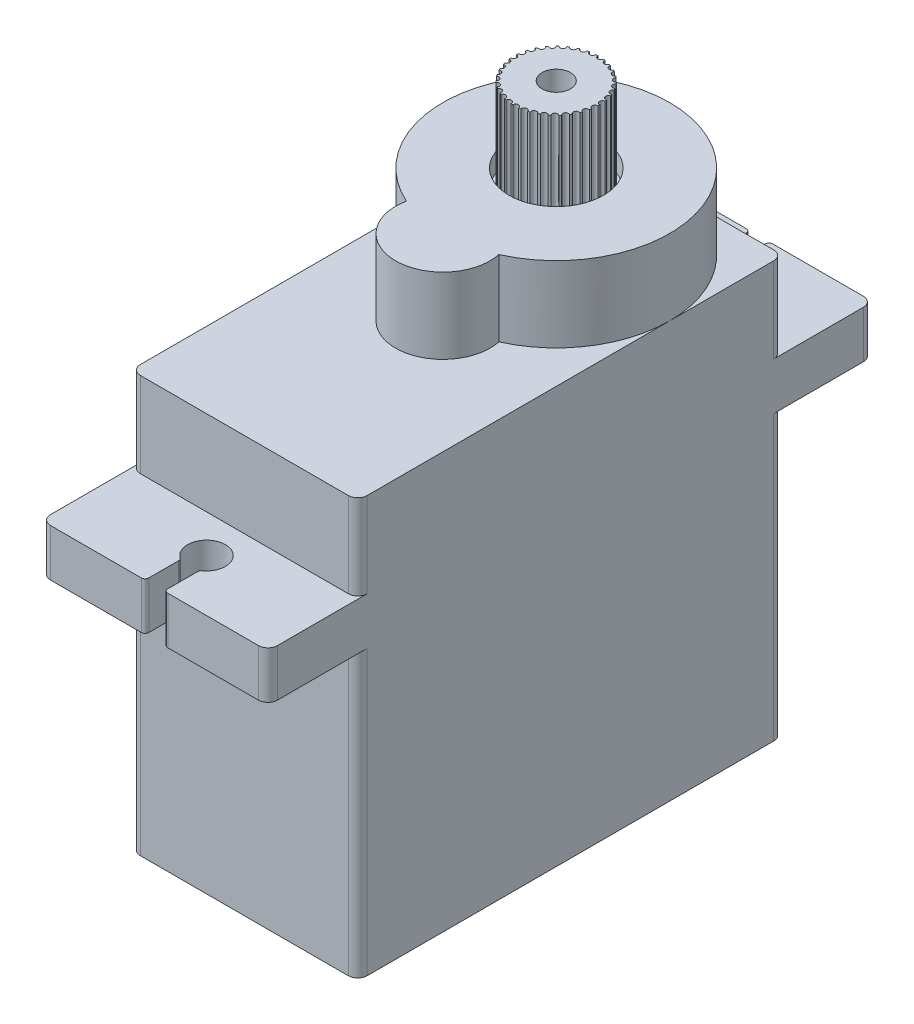
SolidWorks part; units mm, degrees
ref_plane "Ön Düzlem" through (0, 0, 0) normal (0, 0, 1) x (1, 0, 0)
ref_plane "Üst Düzlem" through (0, 0, 0) normal (0, 1, 0) x (1, 0, 0)
ref_plane "Sağ Düzlem" through (0, 0, 0) normal (1, 0, 0) x (0, 0, -1)
sketch "Çizim1" plane through (0, 0, 0) normal (0, 1, 0) x (1, 0, 0)
  line L1 (-5.5, 11.25) -> (5.5, 11.25)
  line L2 (-6, 10.75) -> (-6, -10.75)
  line L3 (-5.5, -11.25) -> (5.5, -11.25)
  line L4 (6, 10.75) -> (6, -10.75)
  line L5 (-6, 11.25) -> (6, -11.25) construction
  line L6 (-6, -11.25) -> (6, 11.25) construction
  arc A0 (5.5, -11.25) -> (6, -10.75) centre (5.5, -10.75) ccw
  arc A1 (-6, -10.75) -> (-5.5, -11.25) centre (-5.5, -10.75) ccw
  arc A2 (5.5, 11.25) -> (6, 10.75) centre (5.5, 10.75) cw
  arc A3 (-5.5, 11.25) -> (-6, 10.75) centre (-5.5, 10.75) ccw
  point P0 (0, 0)
  dimension "D3" = 0.5
  dimension "D1" = 12
  dimension "D2" = 22.5
extrude "Yükseklik-Ekstrüzyon1" add sketch "Çizim1" along normal blind 1
sketch "Çizim2" plane through (0, 1, 0) normal (0, 1, 0) x (1, 0, 0)
  line L0 (-5, 9.25) -> (-5, -9.25)
  line L1 (-5.5, 11.25) -> (5.5, 11.25)
  line L2 (-6, 10.75) -> (-6, -10.75)
  line L3 (-5.5, -11.25) -> (5.5, -11.25)
  line L4 (6, 10.75) -> (6, -10.75)
  line L5 (-6, 11.25) -> (-5.8961, 11.0552) construction
  line L6 (-6, -11.25) -> (-5.8961, -11.0552) construction
  line L7 (-4, -10.25) -> (4, -10.25)
  line L8 (5, 9.25) -> (5, -9.25)
  line L9 (-4, 10.25) -> (4, 10.25)
  line L10 (-6, -11.25) -> (6, -11.25) construction
  line L11 (6, 11.25) -> (6, -11.25) construction
  line L12 (-6, 11.25) -> (-6, -11.25) construction
  line L13 (-6, 11.25) -> (6, 11.25) construction
  line L14 (-5, 10.25) -> (5, 10.25) construction
  line L15 (-5, 10.25) -> (-5, -10.25) construction
  line L16 (-4.9345, 9.2521) -> (4.9345, -9.2521) construction
  line L17 (5, 10.25) -> (5, -10.25) construction
  line L18 (5.8961, 11.0552) -> (6, 11.25) construction
  line L19 (-5, -10.25) -> (5, -10.25) construction
  line L20 (5.8961, -11.0552) -> (6, -11.25) construction
  line L21 (-4.9345, -9.2521) -> (4.9345, 9.2521) construction
  arc A0 (5.5, -11.25) -> (6, -10.75) centre (5.5, -10.75) ccw
  arc A1 (-6, -10.75) -> (-5.5, -11.25) centre (-5.5, -10.75) ccw
  arc A2 (5.5, 11.25) -> (6, 10.75) centre (5.5, 10.75) cw
  arc A3 (-5.5, 11.25) -> (-6, 10.75) centre (-5.5, 10.75) ccw
  arc A5 (4, 10.25) -> (5, 9.25) centre (5, 10.25) ccw
  arc A7 (-4, -10.25) -> (-5, -9.25) centre (-5, -10.25) ccw
  arc A8 (-5, 9.25) -> (-4, 10.25) centre (-5, 10.25) ccw
  arc A9 (5, -9.25) -> (4, -10.25) centre (5, -10.25) ccw
  point P0 (0, 0)
  dimension "D2" = 0.5
  dimension "D1" = 1
extrude "Yükseklik-Ekstrüzyon2" add sketch "Çizim2" along normal blind 5
sketch "Çizim3" plane through (0, 6, 0) normal (0, 1, 0) x (1, 0, 0)
  line L0 (0, -10.25) -> (0, -11.25) construction
  line L1 (-4, -10.25) -> (4, -10.25) construction
  line L2 (-5.5, -11.25) -> (5.5, -11.25) construction
  line L3 (0, -11.25) -> (0, -10.75) construction
  line L4 (0, -10.75) -> (2.4368, -10.75) construction
  line L6 (-2, -10.25) -> (2, -10.25)
  line L7 (-2, -10.25) -> (-2, -11.25)
  line L8 (-2, -11.25) -> (2, -11.25)
  line L9 (2, -10.25) -> (2, -11.25)
  line L10 (-2, -10.25) -> (2, -11.25) construction
  line L11 (-2, -11.25) -> (2, -10.25) construction
  dimension "D1" = 4
extrude "Kes-Ekstrüzyon1" cut sketch "Çizim3" against normal blind 1
fillet "Radyus1" radius 0.1 2 edges at (2, 5, 10.75) (-2, 5, 10.75)
sketch "Çizim4" plane through (0, 6, 0) normal (0, 1, 0) x (1, 0, 0)
  line L0 (-4, 10.25) -> (4, 10.25)
  line L1 (-5.5, 11.25) -> (5.5, 11.25)
  line L2 (-6, 10.75) -> (-6, -10.75)
  line L3 (-5.5, -11.25) -> (5.5, -11.25)
  line L4 (6, 10.75) -> (6, -10.75)
  line L5 (-6, 11.25) -> (-5.8961, 11.0552) construction
  line L6 (-6, -11.25) -> (-5.8961, -11.0552) construction
  line L7 (-4, 10.25) -> (4, 10.25)
  line L8 (5, 9.25) -> (5, -9.25)
  line L9 (5, -9.25) -> (5, 9.25)
  line L10 (-4, 10.25) -> (4, 10.25)
  line L11 (5, 9.25) -> (5, -9.25)
  line L12 (-4, -10.25) -> (4, -10.25)
  line L13 (-5, 9.25) -> (-5, -9.25)
  line L14 (-4.9345, 9.2521) -> (4.9345, -9.2521) construction
  line L15 (-5, 10.25) -> (-5, -10.25) construction
  line L16 (-5, 10.25) -> (5, 10.25) construction
  line L17 (5, 10.25) -> (5, -10.25) construction
  line L18 (5.8961, 11.0552) -> (6, 11.25) construction
  line L19 (5.8961, -11.0552) -> (6, -11.25) construction
  line L20 (-5, -10.25) -> (5, -10.25) construction
  line L21 (-4.9345, -9.2521) -> (4.9345, 9.2521) construction
  arc A0 (5.5, -11.25) -> (6, -10.75) centre (5.5, -10.75) ccw
  arc A1 (-6, -10.75) -> (-5.5, -11.25) centre (-5.5, -10.75) ccw
  arc A2 (5.5, 11.25) -> (6, 10.75) centre (5.5, 10.75) cw
  arc A3 (-5.5, 11.25) -> (-6, 10.75) centre (-5.5, 10.75) ccw
  arc A4 (-5, 9.25) -> (-4, 10.25) centre (-5, 10.25) ccw
  arc A5 (4, 10.25) -> (5, 9.25) centre (5, 10.25) ccw
  arc A6 (-4, -10.25) -> (-5, -9.25) centre (-5, -10.25) ccw
  arc A7 (5, -9.25) -> (4, -10.25) centre (5, -10.25) ccw
  arc A8 (5, 10.25) -> (5, 10.25) centre (5, 10.25) cw
  arc A9 (5, -10.25) -> (5, -10.25) centre (5, -10.25) ccw
  arc A10 (-5, -10.25) -> (-5, -10.25) centre (-5, -10.25) ccw
  arc A11 (-5, 10.25) -> (-5, 10.25) centre (-5, 10.25) ccw
  point P0 (0, 0)
  line M12 (4, -10.25) -> (2, -10.25)
  line M14 (2, -11.25) -> (5.5, -11.25)
  arc M15 (5.5, -11.25) -> (6, -10.75) centre (5.5, -10.75) ccw
  line M16 (6, -10.75) -> (6, 10.75)
  arc M17 (6, 10.75) -> (5.5, 11.25) centre (5.5, 10.75) ccw
  line M18 (5.5, 11.25) -> (-5.5, 11.25)
  arc M19 (-5.5, 11.25) -> (-6, 10.75) centre (-5.5, 10.75) ccw
  line M20 (-6, 10.75) -> (-6, -10.75)
  arc M21 (-6, -10.75) -> (-5.5, -11.25) centre (-5.5, -10.75) ccw
  line M22 (-5.5, -11.25) -> (-2, -11.25)
  line M24 (-2, -10.25) -> (-4, -10.25)
  arc M25 (-4, -10.25) -> (-5, -9.25) centre (-5, -10.25) ccw
  line M26 (-5, -9.25) -> (-5, 9.25)
  arc M27 (-5, 9.25) -> (-4, 10.25) centre (-5, 10.25) ccw
  line M28 (-4, 10.25) -> (4, 10.25)
  arc M29 (4, 10.25) -> (5, 9.25) centre (5, 10.25) ccw
  line M30 (5, 9.25) -> (5, -9.25)
  arc M31 (5, -9.25) -> (4, -10.25) centre (5, -10.25) ccw
  dimension "D1" = 0.5
  dimension "D2" = 1
extrude "Yükseklik-Ekstrüzyon4" add sketch "Çizim4" along normal blind 9 contours M31 M12 M14 M15 M16 M17 M18 M19 M20 M21 M22 M24 M25 M26 M27 M28 M29 M30 | L12 L3 region at (0, 6, -10.995)
sketch "Çizim6" plane through (0, 15, 0) normal (0, 1, 0) x (1, 0, 0)
  line L0 (0, -10.25) -> (0, -12.25) construction
  line L1 (-5.5, 16) -> (-0.7, 16)
  line L2 (-6, 15.5) -> (-6, -15.5)
  line L3 (-5.5, -16) -> (-0.7, -16)
  line L4 (6, 15.5) -> (6, -15.5)
  line L5 (-6, 16) -> (6, -16) construction
  line L6 (-3.8437, -10.25) -> (6, 16) construction
  line L7 (-4, 10.25) -> (4, 10.25)
  line L8 (-5, 9.25) -> (-5, -9.25)
  line L9 (-4, -10.25) -> (4, -10.25)
  line L10 (5, 9.25) -> (5, -9.25)
  line L11 (-4.5616, 9.3512) -> (4.5616, -9.3512) construction
  line L12 (-4.5616, -9.3512) -> (4.5616, 9.3512) construction
  line L13 (0, -12.25) -> (0, -11.25) construction
  line L14 (-5.5, -11.25) -> (5.5, -11.25) construction
  line L15 (0, -11.25) -> (8.7476, -11.25) construction
  line L16 (0, -12.25) -> (8.7476, -12.25) construction
  line L17 (0.7, -16) -> (5.5, -16)
  line L18 (-0.5, -14.2247) -> (-0.5, -15.8)
  line L19 (0.5, -14.2247) -> (0.5, -15.8)
  line L20 (0, 0) -> (5, 0) construction
  line L21 (0.5, 14.2247) -> (0.5, 15.8)
  line L22 (-0.5, 14.2247) -> (-0.5, 15.8)
  line L23 (0.7, 16) -> (5.5, 16)
  arc A0 (-5, 9.25) -> (-4, 10.25) centre (-5, 10.25) ccw
  arc A1 (4, 10.25) -> (5, 9.25) centre (5, 10.25) ccw
  arc A2 (5, -9.25) -> (4, -10.25) centre (5, -10.25) ccw
  arc A3 (-4, -10.25) -> (-5, -9.25) centre (-5, -10.25) ccw
  arc A4 (5.5, -16) -> (6, -15.5) centre (5.5, -15.5) ccw
  arc A5 (-6, -15.5) -> (-5.5, -16) centre (-5.5, -15.5) ccw
  arc A6 (5.5, 16) -> (6, 15.5) centre (5.5, 15.5) cw
  arc A7 (-5.5, 16) -> (-6, 15.5) centre (-5.5, 15.5) ccw
  arc A9 (0.5833, -14.0622) -> (-0.5833, -14.0622) centre (0, -13.25) ccw
  arc A10 (0.5, -14.2247) -> (0.5833, -14.0622) centre (0.7, -14.2247) cw
  arc A11 (-0.5, -14.2247) -> (-0.5833, -14.0622) centre (-0.7, -14.2247) ccw
  arc A12 (0.5, -15.8) -> (0.7, -16) centre (0.7, -15.8) ccw
  arc A13 (-0.5, -15.8) -> (-0.7, -16) centre (-0.7, -15.8) cw
  arc A14 (0.5, 15.8) -> (0.7, 16) centre (0.7, 15.8) cw
  arc A15 (-0.5, 15.8) -> (-0.7, 16) centre (-0.7, 15.8) ccw
  arc A16 (0.5, 14.2247) -> (0.5833, 14.0622) centre (0.7, 14.2247) ccw
  arc A17 (-0.5, 14.2247) -> (-0.5833, 14.0622) centre (-0.7, 14.2247) cw
  arc A18 (0.5833, 14.0622) -> (-0.5833, 14.0622) centre (0, 13.25) cw
  point P0 (0, 0)
  point P6 (0, 0)
  point P54 (0.5, -16)
  dimension "D2" = 0.5
  dimension "D4" = 2
  dimension "D5" = 0.2
  dimension "D1" = 32
  dimension "D3" = 1
extrude "Yükseklik-Ekstrüzyon5" add sketch "Çizim6" along normal blind 2.5
sketch "Çizim7" plane through (0, 17.5, 0) normal (0, 1, 0) x (1, 0, 0)
  line L0 (6, -15.5) -> (6, 15.5) construction
  line L1 (-5.5, 11.25) -> (5.5, 11.25)
  line L2 (-6, 10.75) -> (-6, -10.75)
  line L3 (-5.5, -11.25) -> (5.5, -11.25)
  line L4 (6, 10.75) -> (6, -10.75)
  line L5 (-6, 11.25) -> (-5.8961, 11.0552) construction
  line L6 (-6, -11.25) -> (-5.8961, -11.0552) construction
  line L7 (-5, 9.25) -> (-5, -9.25)
  line L8 (-4, 10.25) -> (4, 10.25)
  line L9 (5, 9.25) -> (5, -9.25)
  line L10 (4, -10.25) -> (-4, -10.25)
  line L12 (-4.9345, 9.2521) -> (4.9345, -9.2521) construction
  line L13 (5.8961, 11.0552) -> (6, 11.25) construction
  line L14 (5.8961, -11.0552) -> (6, -11.25) construction
  line L15 (-5, -9.25) -> (-5, 9.25)
  line L16 (-4.9345, -9.2521) -> (4.9345, 9.2521) construction
  line L17 (-5, 9.25) -> (-5, -9.25)
  arc A0 (-6, -10.75) -> (-5.5, -11.25) centre (-5.5, -10.75) ccw
  arc A1 (5.5, -11.25) -> (6, -10.75) centre (5.5, -10.75) ccw
  arc A2 (5.5, 11.25) -> (6, 10.75) centre (5.5, 10.75) cw
  arc A3 (-5.5, 11.25) -> (-6, 10.75) centre (-5.5, 10.75) ccw
  arc A4 (-5, 9.25) -> (-4, 10.25) centre (-5, 10.25) ccw
  arc A5 (4, 10.25) -> (5, 9.25) centre (5, 10.25) ccw
  arc A6 (5, -9.25) -> (4, -10.25) centre (5, -10.25) ccw
  arc A8 (-4, -10.25) -> (-5, -9.25) centre (-5, -10.25) ccw
  point P0 (0, 0)
  line M16 (6, -15.5) -> (6, 15.5)
  line M28 (-6, 15.5) -> (-6, -15.5)
  line M39 (-5, -9.25) -> (-5, 9.25)
  arc M40 (-5, 9.25) -> (-4, 10.25) centre (-5, 10.25) ccw
  line M41 (-4, 10.25) -> (4, 10.25)
  arc M42 (4, 10.25) -> (5, 9.25) centre (5, 10.25) ccw
  line M43 (5, 9.25) -> (5, -9.25)
  arc M44 (5, -9.25) -> (4, -10.25) centre (5, -10.25) ccw
  line M45 (4, -10.25) -> (-4, -10.25)
  arc M46 (-4, -10.25) -> (-5, -9.25) centre (-5, -10.25) ccw
  dimension "D2" = 0.5
  dimension "D1" = 22.5
extrude "Yükseklik-Ekstrüzyon6" add sketch "Çizim7" along normal blind 3.5 contours L1 A3 A0 L3 A1 A2 M28 M16 M46 M39 M40 M41 M42 M43 M44 M45 region at (0, 17.5, -10.995)
sketch "Çizim8" plane through (0, 21, 0) normal (0, 1, 0) x (1, 0, 0)
  line L0 (6, -15.5) -> (6, -10.75) construction
  line L1 (-5.5, 11.25) -> (5.5, 11.25)
  line L2 (-6, 10.75) -> (-6, -10.75)
  line L3 (-5.5, -11.25) -> (5.5, -11.25)
  line L4 (6, 10.75) -> (6, -10.75)
  line L5 (-6, 11.25) -> (6, -11.25) construction
  line L6 (-6, -11.25) -> (6, 11.25) construction
  arc A0 (-6, -10.75) -> (-5.5, -11.25) centre (-5.5, -10.75) ccw
  arc A1 (5.5, -11.25) -> (6, -10.75) centre (5.5, -10.75) ccw
  arc A2 (5.5, 11.25) -> (6, 10.75) centre (5.5, 10.75) cw
  arc A3 (-5.5, 11.25) -> (-6, 10.75) centre (-5.5, 10.75) ccw
  point P0 (0, 0)
  dimension "D1" = 0.5
extrude "Yükseklik-Ekstrüzyon7" add sketch "Çizim8" along normal blind 1
sketch "Çizim9" plane through (0, 22, 0) normal (0, 1, 0) x (1, 0, 0)
  line L0 (-6, 5.25) -> (6, 5.25) construction
  line L1 (-6, 10.75) -> (-6, -10.75) construction
  line L2 (6, -10.75) -> (6, 10.75) construction
  line L3 (5.5, 11.25) -> (-5.5, 11.25) construction
  line L4 (0, 5.25) -> (0, -0.75) construction
  arc A0 (2.4451, -0.2292) -> (-2.4451, -0.2292) centre (0, 5.25) ccw
  arc A1 (-2.4451, -0.2292) -> (2.4451, -0.2292) centre (0, -0.75) ccw
  arc A2 (1.0153, 0.3542) -> (-1.0153, 0.3542) centre (0, 5.25) ccw
  arc A3 (-1.0153, 0.3542) -> (1.0153, 0.3542) centre (0, -0.75) ccw
  dimension "D2" = 5
  dimension "D1" = 6
  dimension "D3" = 1
extrude "Kes-Ekstrüzyon2" cut sketch "Çizim9" against normal blind 1 contours A2 A3
extrude "Yükseklik-Ekstrüzyon8" add sketch "Çizim9<3>" along normal blind 3
sketch "Çizim9<3>" plane through (0, 22, 0) normal (0, 1, 0) x (1, 0, 0) same geometry as "Çizim9"
fillet "Radyus2" radius 0.5 2 edges at (1.0153, 23, -0.3542) (-1.0153, 23, -0.3542)
sketch "Çizim10" plane through (0, 25, 0) normal (0, 1, 0) x (1, 0, 0)
  arc A0 (2.4451, -0.2292) -> (-2.4451, -0.2292) centre (0, 5.25) ccw
  arc A1 (-2.4451, -0.2292) -> (2.4451, -0.2292) centre (0, -0.75) ccw
extrude "Yükseklik-Ekstrüzyon9" add sketch "Çizim10" along normal blind 1
sketch "Çizim11" plane through (0, 26, 0) normal (0, 1, 0) x (1, 0, 0)
  circle A0 centre (0, 5.25) radius 2.5
  dimension "D1" = 5
extrude "Kes-Ekstrüzyon3" cut sketch "Çizim11" against normal blind 10
sketch "Çizim15" plane through (0, 26, 0) normal (0, 1, 0) x (1, 0, 0)
  circle A0 centre (0, -0.75) radius 0.25
  dimension "D1" = 0.5
extrude "Yükseklik-Ekstrüzyon12" add sketch "Çizim15" against normal blind 11
ref_plane "Düzlem3" through (0, 30, 0) normal (0, 1, 0) x (1, 0, 0)
sketch "Çizim19" plane through (0, 30, 0) normal (0, 1, 0) x (1, 0, 0)
  circle A0 centre (0, 5.25) radius 2.25
  dimension "D1" = 4.5
extrude "Yükseklik-Ekstrüzyon17" add sketch "Çizim19" against normal blind 5 separate body
sketch "Çizim20" plane through (0, 25, 0) normal (0, -1, 0) x (1, 0, 0)
  circle A0 centre (0, -5.25) radius 4.75
  dimension "D1" = 9.5
extrude "Yükseklik-Ekstrüzyon18" add sketch "Çizim20" along normal blind 3
sketch "Çizim21" plane through (0, 30, 0) normal (0, 1, 0) x (1, 0, 0)
  circle A0 centre (0, 5.25) radius 0.75
  dimension "D1" = 1.5
extrude "Kes-Ekstrüzyon5" cut sketch "Çizim21" against normal blind 10
ref_plane "Düzlem4" through (0, 25.5, 0) normal (0, 1, 0) x (1, 0, 0)
sketch "Çizim22" plane through (0, 25.5, 0) normal (0, 1, 0) x (1, 0, 0)
  line L0 (0, 11.25) -> (0, -3.25) construction
  arc A0 (2.4451, -0.2292) -> (-2.4451, -0.2292) centre (0, 5.25) ccw construction
  arc A1 (-2.4451, -0.2292) -> (2.4451, -0.2292) centre (0, -0.75) ccw construction
  circle A2 centre (0, -0.75) radius 0.5
  dimension "D1" = 1
extrude "Yükseklik-Ekstrüzyon19" add sketch "Çizim22" against normal blind 5
sketch "Çizim23" plane through (0, 20.5, 0) normal (0, -1, 0) x (1, 0, 0)
  circle A0 centre (0, 0.75) radius 4
  dimension "D1" = 8
extrude "Yükseklik-Ekstrüzyon20" add sketch "Çizim23" along normal blind 2
sketch "Çizim24" plane through (0, 22, 0) normal (0, -1, 0) x (1, 0, 0)
  circle A0 centre (0, -5.25) radius 0.75
extrude "Yükseklik-Ekstrüzyon21" add sketch "Çizim24" along normal blind 7 separate body
ref_plane "Düzlem5" through (0, 19, 0) normal (0, -1, 0) x (-1, 0, 0)
sketch "Çizim25" plane through (0, 19, 0) normal (0, -1, 0) x (-1, 0, 0)
  circle A0 centre (0, 5.25) radius 3.5
  dimension "D1" = 7
extrude "Yükseklik-Ekstrüzyon22" add sketch "Çizim25" along normal blind 1
ref_plane "Düzlem6" through (0, 17.5, 0) normal (0, -1, 0) x (-1, 0, 0)
sketch "Çizim26" plane through (0, 17.5, 0) normal (0, -1, 0) x (-1, 0, 0)
  circle A0 centre (0, -0.75) radius 4.5
  dimension "D1" = 9
extrude "Yükseklik-Ekstrüzyon23" add sketch "Çizim26" along normal blind 1
sketch "Çizim32" plane through (0, 0, 10.25) normal (0, 0, -1) x (-1, 0, 0)
  line L1 (2, 6) -> (-2, 6)
  line L2 (2, 6) -> (2, 5.1)
  line L3 (1.9, 5) -> (-1.9, 5)
  line L4 (-2, 6) -> (-2, 5.1)
  arc A0 (-1.9, 5) -> (-2, 5.1) centre (-1.9, 5.1) cw
  arc A1 (2, 5.1) -> (1.9, 5) centre (1.9, 5.1) cw
  point P7 (-2, 5)
  dimension "D3" = 0.1
  dimension "D1" = 1
  dimension "D2" = 4
extrude "Kes-Ekstrüzyon7" cut sketch "Çizim32" along normal blind 30
sketch "Çizim33" plane through (0, 0, 11.25) normal (0, 0, 1) x (1, 0, 0)
  line L1 (-2, 6) -> (2, 6)
  line L2 (-2, 6) -> (-2, 5.1)
  line L3 (-1.9, 5) -> (1.9, 5)
  line L4 (2, 6) -> (2, 5.1)
  arc A0 (1.9, 5) -> (2, 5.1) centre (1.9, 5.1) ccw
  arc A1 (-2, 5.1) -> (-1.9, 5) centre (-1.9, 5.1) ccw
  point P7 (2, 5)
  point P10 (-2, 5)
  dimension "D3" = 0.1
  dimension "D1" = 1
  dimension "D2" = 4
extrude "Yükseklik-Ekstrüzyon33" add sketch "Çizim33" against normal blind 1
sketch "Çizim34" plane through (0, 1, 0) normal (0, 1, 0) x (1, 0, 0)
  line L0 (-5, -6.25) -> (5, -6.25) construction
  line L1 (-5, 9.25) -> (-5, -9.25) construction
  line L2 (5, -9.25) -> (5, 9.25) construction
  line L3 (-4, -10.25) -> (4, -10.25) construction
  line L5 (-3, -3.25) -> (3, -3.25)
  line L6 (-4, -4.25) -> (-4, -8.25)
  line L7 (-3, -9.25) -> (3, -9.25)
  line L8 (4, -4.25) -> (4, -8.25)
  line L9 (-4, -3.25) -> (4, -9.25) construction
  line L10 (-4, -9.25) -> (4, -3.25) construction
  arc A0 (3, -9.25) -> (4, -8.25) centre (3, -8.25) ccw
  arc A1 (-4, -8.25) -> (-3, -9.25) centre (-3, -8.25) ccw
  arc A2 (3, -3.25) -> (4, -4.25) centre (3, -4.25) cw
  arc A3 (-3, -3.25) -> (-4, -4.25) centre (-3, -4.25) ccw
  point P8 (0, -6.25)
  dimension "D4" = 1
  dimension "D1" = 4
  dimension "D2" = 6
  dimension "D3" = 8
extrude "Yükseklik-Ekstrüzyon34" add sketch "Çizim34" along normal blind 14
ref_plane "Düzlem8" through (0, 1, 0) normal (0, -1, 0) x (-1, 0, 0)
sketch "Çizim37" plane through (0, 1, 0) normal (0, -1, 0) x (-1, 0, 0)
  line L0 (4, -6.25) -> (-4, -6.25) construction
  line L1 (4, -4.25) -> (4, -8.25) construction
  line L2 (-4, -8.25) -> (-4, -4.25) construction
  line L4 (4, -9.25) -> (-4, -9.25)
  line L5 (4, -9.25) -> (4, -3.25)
  line L6 (4, -3.25) -> (-4, -3.25)
  line L7 (-4, -9.25) -> (-4, -3.25)
  line L8 (4, -9.25) -> (-4, -3.25) construction
  line L9 (4, -3.25) -> (-4, -9.25) construction
  point P6 (0, -6.25)
  dimension "D1" = 6
  dimension "D2" = 8
extrude "Yükseklik-Ekstrüzyon36" add sketch "Çizim37" against normal blind 1
ref_plane "Düzlem9" through (0, 0, -10.75) normal (0, 0, -1) x (-1, 0, 0)
sketch "Çizim39" plane through (0, 0, -10.75) normal (0, 0, -1) x (-1, 0, 0)
  line L0 (0, 0) -> (0, 6.0146) construction
  line L1 (-5.5, 0) -> (5.5, 0) construction
  line L2 (-2, 6.0146) -> (2, 6.0146)
  line L4 (-2, 6.0146) -> (-2, 5.0146)
  line L5 (-2, 5.0146) -> (2, 5.0146)
  line L6 (2, 6.0146) -> (2, 5.0146)
  line L7 (0, 6.0146) -> (2, 5.0146) construction
  line L8 (-2, 5.0146) -> (0, 6.0146) construction
extrude "Yükseklik-Ekstrüzyon37" add sketch "Çizim39" along normal blind 0.1
sketch "Çizim40" plane through (0, 0, -10.85) normal (0, 0, -1) x (-1, 0, 0)
  line L0 (-2, 5.55) -> (2, 5.55) construction
  line L1 (-2, 6) -> (-2, 5.1) construction
  line L2 (2, 5.1) -> (2, 6) construction
  circle A0 centre (0, 5.55) radius 0.4
  circle A1 centre (1, 5.55) radius 0.4
  circle A2 centre (-1, 5.55) radius 0.4
  dimension "D1" = 0.8
  dimension "D2" = 1
  dimension "D3" = 1
extrude "Yükseklik-Ekstrüzyon38" add sketch "Çizim40" along normal blind 2
sketch "Çizim41" plane through (0, 30, 0) normal (0, 1, 0) x (1, 0, 0)
  line L0 (0, 5.25) -> (-2.25, 5.25) construction
  circle A0 centre (0, 5.25) radius 2.25
  circle A1 centre (-2.25, 5.25) radius 0.15
  circle A2 centre (-2.2138, 5.6518) radius 0.15
  circle A3 centre (-2.1065, 6.0406) radius 0.15
  circle A4 centre (-1.9315, 6.404) radius 0.15
  circle A5 centre (-1.6944, 6.7304) radius 0.15
  circle A6 centre (-1.4029, 7.0091) radius 0.15
  circle A7 centre (-1.0662, 7.2313) radius 0.15
  circle A8 centre (-0.6953, 7.3899) radius 0.15
  circle A9 centre (-0.302, 7.4796) radius 0.15
  circle A10 centre (0.1009, 7.4977) radius 0.15
  circle A11 centre (0.5007, 7.4436) radius 0.15
  circle A12 centre (0.8843, 7.3189) radius 0.15
  circle A13 centre (1.2395, 7.1278) radius 0.15
  circle A14 centre (1.5549, 6.8763) radius 0.15
  circle A15 centre (1.8203, 6.5725) radius 0.15
  circle A16 centre (2.0272, 6.2262) radius 0.15
  circle A17 centre (2.1689, 5.8486) radius 0.15
  circle A18 centre (2.2409, 5.4517) radius 0.15
  circle A19 centre (2.2409, 5.0483) radius 0.15
  circle A20 centre (2.1689, 4.6514) radius 0.15
  circle A21 centre (2.0272, 4.2738) radius 0.15
  circle A22 centre (1.8203, 3.9275) radius 0.15
  circle A23 centre (1.5549, 3.6237) radius 0.15
  circle A24 centre (1.2395, 3.3722) radius 0.15
  circle A25 centre (0.8843, 3.1811) radius 0.15
  circle A26 centre (0.5007, 3.0564) radius 0.15
  circle A27 centre (0.1009, 3.0023) radius 0.15
  circle A28 centre (-0.302, 3.0204) radius 0.15
  circle A29 centre (-0.6953, 3.1101) radius 0.15
  circle A30 centre (-1.0662, 3.2687) radius 0.15
  circle A31 centre (-1.4029, 3.4909) radius 0.15
  circle A32 centre (-1.6944, 3.7696) radius 0.15
  circle A33 centre (-1.9315, 4.096) radius 0.15
  circle A34 centre (-2.1065, 4.4594) radius 0.15
  circle A35 centre (-2.2138, 4.8482) radius 0.15
  point P75 (0, 5.25)
  dimension "D1" = 0.3
  dimension "D2" = 35
extrude "Kes-Ekstrüzyon8" cut sketch "Çizim41" against normal blind 5 contours A1 A0 | A1 L0 A0 | L0 A1 | A3 | A2 | A35 | A34 | A33 | A32 | A31 | A30 | A29 | A28 | A27 | A26 | A25 | A24 | A23 | A22 | A21 | A20 | A19 | A18 | A17 | A16 | A15 | A14 | A13 | A12 | A11 | A10 | A9 | A8 | A7 | A6 | A5 | A4 region at (-2.1854, 30, -5.187) region at (-2.1854, 30, -5.313) region at (-2.3128, 30, -5.25)
move or copy body "Body-Move/Copy1" [suppressed] bodies to move or copy 125 138
